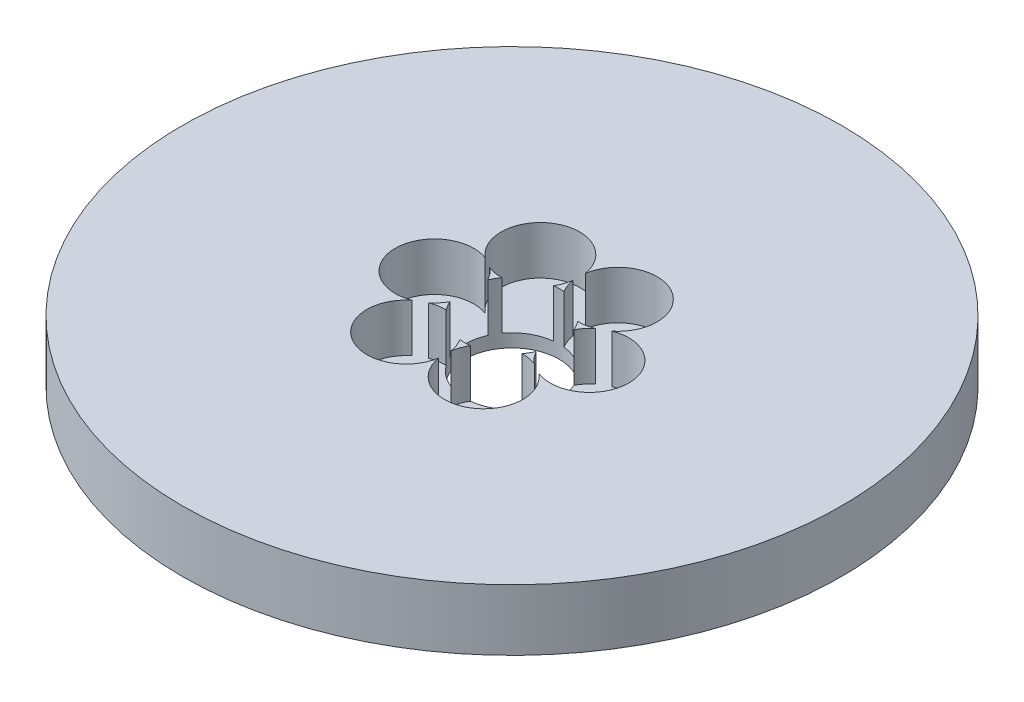
SolidWorks part; units mm, degrees
ref_plane "Front Plane" through (0, 0, 0) normal (0, 0, 1) x (1, 0, 0)
ref_plane "Top Plane" through (0, 0, 0) normal (0, 1, 0) x (1, 0, 0)
ref_plane "Right Plane" through (0, 0, 0) normal (1, 0, 0) x (0, 0, -1)
sketch "Sketch1" plane through (0, 0, 0) normal (0, 1, 0) x (1, 0, 0)
  circle A0 centre (0, 0) radius 70
  dimension "FLANGE_OD" = 140
extrude "Boss-Extrude1" add sketch "Sketch1" along normal blind 13
sketch "Sketch2" plane through (0, 0, 0) normal (0, 1, 0) x (1, 0, 0)
  circle A0 centre (0, 0) radius 10
  dimension "BORE_D" = 20
extrude "Cut-Extrude1" cut sketch "Sketch2" along normal through all
sketch "Sketch3" plane through (0, 13, 0) normal (0, 1, 0) x (1, 0, 0)
  circle A0 centre (0, 0) radius 16.4634 construction
  circle A1 centre (-16.4634, 0) radius 8.3341
  dimension "BOLT_D" = 16.6682
  dimension "BOLT_PCD" = 32.9269
extrude "Cut-Extrude2" cut sketch "Sketch3" against normal blind 10.2208
pattern_circular "CirPattern1" count 6 over 360 about axis through (0, 0, 0) along (0, 1, 0) of "Cut-Extrude2"
